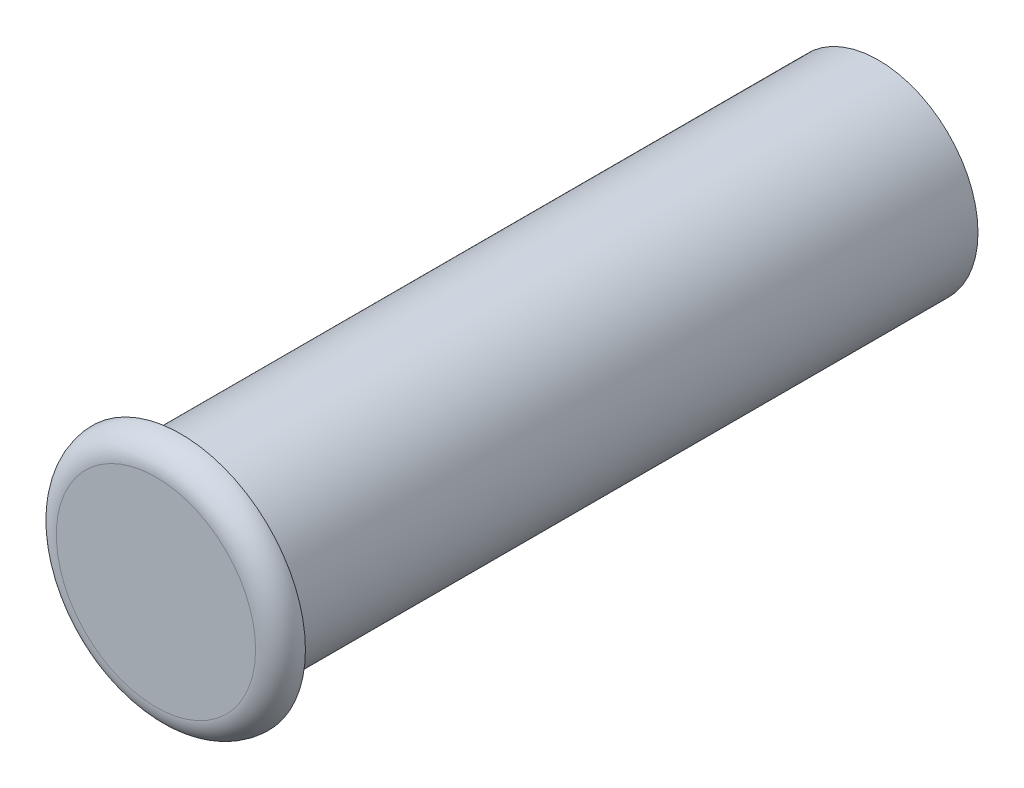
SolidWorks part; units mm, degrees
ref_plane "前视基准面" through (0, 0, 0) normal (0, 0, 1) x (1, 0, 0)
ref_plane "上视基准面" through (0, 0, 0) normal (0, 1, 0) x (1, 0, 0)
ref_plane "右视基准面" through (0, 0, 0) normal (1, 0, 0) x (0, 0, -1)
sketch "草图1" plane through (0, 0, 0) normal (0, 0, 1) x (1, 0, 0)
  circle A0 centre (0, 0) radius 2
  dimension "D1" = 4
extrude "凸台-拉伸1" add sketch "草图1" along normal mid plane 14
sketch "草图2" plane through (0, 0, 7) normal (0, 0, 1) x (1, 0, 0)
  circle A0 centre (0, 0) radius 2.5
  dimension "D1" = 5
extrude "凸台-拉伸2" add sketch "草图2" along normal blind 0.5
fillet "圆角1" radius 0.5 1 edges at (2.5, 0, 7.5)
sketch "草图3" plane through (0, 0, -7) normal (0, 0, -1) x (-1, 0, 0)
  circle A0 centre (0, 0) radius 1.5
  dimension "D1" = 3
extrude "切除-拉伸1" cut sketch "草图3" against normal blind 14
